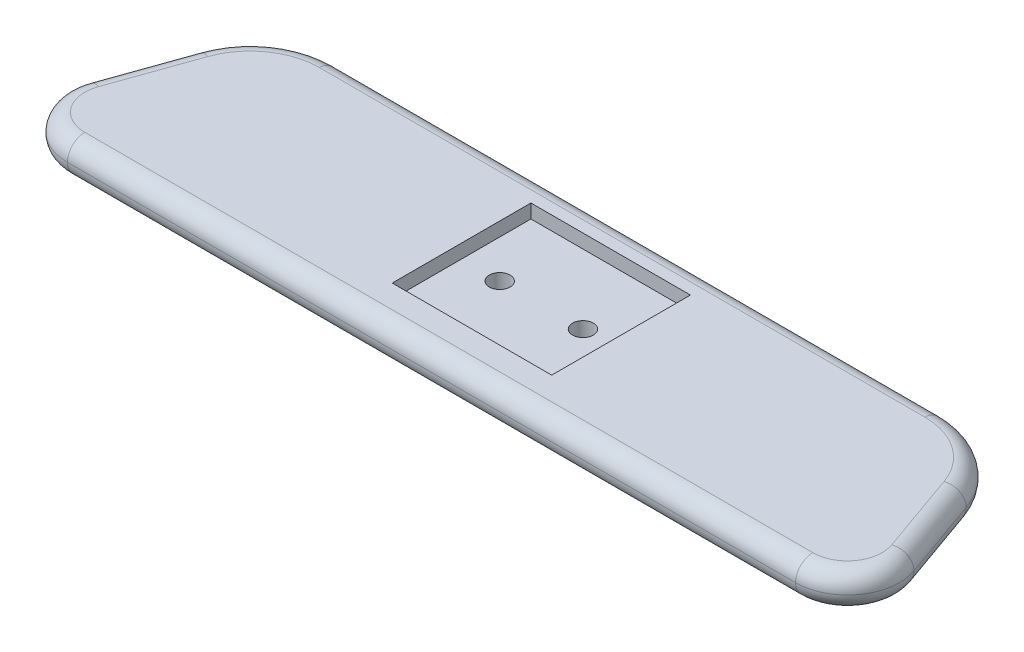
SolidWorks part; units mm, degrees
material "Oak"
ref_plane "Front" through (0, 0, 0) normal (0, 0, 1) x (1, 0, 0)
ref_plane "Top" through (0, 0, 0) normal (0, 1, 0) x (1, 0, 0)
ref_plane "Right" through (0, 0, 0) normal (1, 0, 0) x (0, 0, -1)
sketch "Sketch1" plane through (0, 0, 0) normal (0, 1, 0) x (1, 0, 0)
  line L0 (-105, -31.6761) -> (105, -31.6761)
  line L1 (119.1396, -11.669) -> (110.8752, 11.669)
  line L2 (87.3091, 28.3239) -> (-87.3091, 28.3239)
  line L3 (-110.8752, 11.669) -> (-119.1396, -11.669)
  arc A0 (-105, -31.6761) -> (-119.1396, -11.669) centre (-105, -16.6761) cw
  arc A1 (105, -31.6761) -> (119.1396, -11.669) centre (105, -16.6761) ccw
  arc A2 (-87.3091, 28.3239) -> (-110.8752, 11.669) centre (-87.3091, 3.3239) ccw
  arc A3 (110.8752, 11.669) -> (87.3091, 28.3239) centre (87.3091, 3.3239) ccw
  point P4 (0, 28.3239)
  point P5 (115.0074, 0)
  point P13 (-104.9774, 28.3239)
  dimension "D4" = 15
  dimension "D5" = 15
  dimension "D6" = 25
  dimension "D7" = 25
  dimension "D1" = 70.5
  dimension "D2" = 210
  dimension "D3" = 60
extrude "Boss-Extrude1" add sketch "Sketch1" along normal mid plane 10
sketch "Sketch2" plane through (0, 5, 0) normal (0, 1, 0) x (1, 0, 0)
  line L1 (-23, 20) -> (23, 20)
  line L2 (-23, 20) -> (-23, -20)
  line L3 (-23, -20) -> (23, -20)
  line L4 (23, 20) -> (23, -20)
  line L5 (-23, 20) -> (23, -20) construction
  line L6 (-23, -20) -> (23, 20) construction
  point P0 (0, 0)
  dimension "D1" = 40
  dimension "D2" = 46
extrude "Cut-Extrude1" cut sketch "Sketch2" against normal blind 4 and the other way through all
sketch "Sketch3" plane through (0, 1, 0) normal (0, 1, 0) x (1, 0, 0)
  circle A0 centre (12, 0) radius 3
  circle A1 centre (-12, 0) radius 3
  dimension "D1" = 6
  dimension "D2" = 12
  dimension "D3" = 12
extrude "Cut-Extrude2" cut sketch "Sketch3" against normal through all
sketch "Sketch4" plane through (0, -5, 0) normal (0, -1, 0) x (1, 0, 0)
  line L0 (87.3091, -28.3239) -> (-87.3091, -28.3239) construction
  circle A0 centre (-70, 9.6761) radius 2
  circle A1 centre (-70, -6.3239) radius 2
  circle A2 centre (70, -6.3239) radius 2
  circle A3 centre (70, 9.6761) radius 2
  dimension "D1" = 4
  dimension "D2" = 38
  dimension "D3" = 22
  dimension "D4" = 70
  dimension "D5" = 70
extrude "Cut-Extrude3" cut sketch "Sketch4" against normal blind 8
fillet "Fillet1" radius 5 16 edges at (101.7378, -5, -23.7399) (115.0074, -5, 0) (117.2496, -5, 25.3333) (0, -5, 31.6761) (-117.2496, -5, 25.3333) (-115.0074, -5, 0) (-101.7378, -5, -23.7399) (-117.2496, 5, 25.3333) (-115.0074, 5, 0) (-101.7378, 5, -23.7399) (0, 5, -28.3239) (101.7378, 5, -23.7399) (115.0074, 5, 0) (117.2496, 5, 25.3333) (0, -5, -28.3239) (0, 5, 31.6761)
sketch "Sketch5" plane through (0, 5, 0) normal (0, 1, 0) x (1, 0, 0)
  line L0 (-150, -10) -> (50, -10) construction
  text T0 "RER" font "Century Gothic" height 20
  dimension "D1" = 10
  dimension "D2" = 200
  dimension "D3" = 50
extrude "Cut-Extrude8" [suppressed] cut sketch "Sketch5" against normal blind 2
